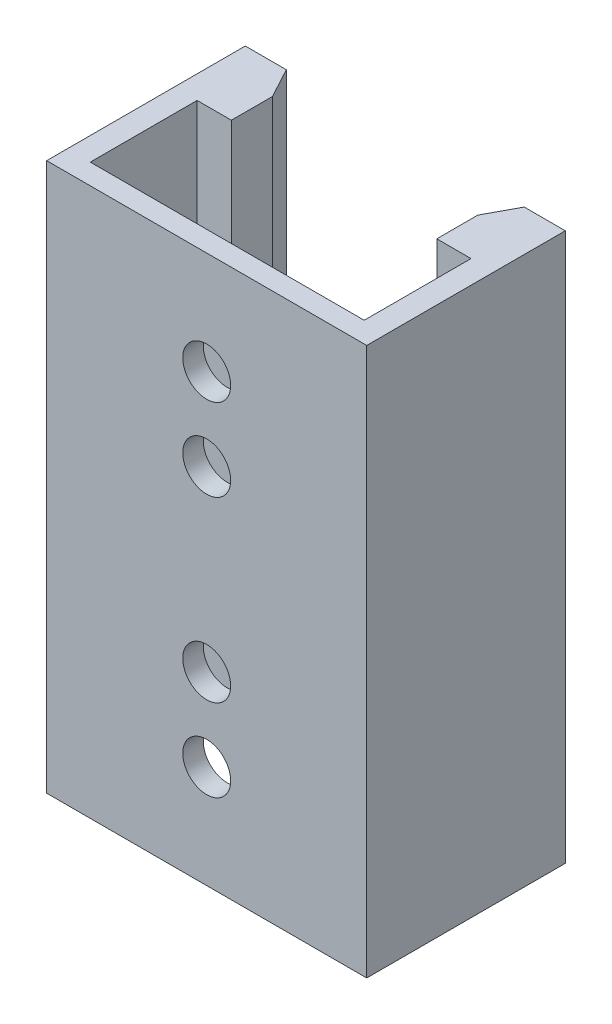
SolidWorks part; units mm, degrees
ref_plane "Front Plane" through (0, 0, 0) normal (0, 0, 1) x (1, 0, 0)
ref_plane "Top Plane" through (0, 0, 0) normal (0, 1, 0) x (1, 0, 0)
ref_plane "Right Plane" through (0, 0, 0) normal (1, 0, 0) x (0, 0, -1)
sketch "Sketch1" plane through (0, 0, 0) normal (0, 1, 0) x (1, 0, 0)
  line L0 (-11.6838, 0) -> (11.6838, 0)
  line L1 (11.6838, 0) -> (11.6838, 14.5)
  line L2 (11.6838, 14.5) -> (8.6838, 14.5)
  line L3 (8.6838, 14.5) -> (7.5, 12.3)
  line L4 (7.5, 12.3) -> (7.5, 9.3)
  line L5 (7.5, 9.3) -> (10, 9.3)
  line L6 (10, 9.3) -> (10, 1.5)
  line L7 (10, 1.5) -> (-10, 1.5)
  line L8 (0, 1.5) -> (0, 0)
  line L9 (-10, 9.3) -> (-10, 1.5)
  line L10 (-7.5, 9.3) -> (-10, 9.3)
  line L11 (-7.5, 12.3) -> (-7.5, 9.3)
  line L12 (-8.6838, 14.5) -> (-7.5, 12.3)
  line L13 (-11.6838, 14.5) -> (-8.6838, 14.5)
  line L14 (-11.6838, 0) -> (-11.6838, 14.5)
  dimension "D1" = 10
  dimension "D2" = 7.8
  dimension "D3" = 2.5
  dimension "D4" = 3
  dimension "D5" = 2.2
  dimension "D6" = 3
  dimension "D7" = 14.5
extrude "Boss-Extrude1" add sketch "Sketch1" along normal blind 40 contours L7 L9 L10 L11 L12 L13 L14 L0 L1 L2 L3 L4 L5 L6
sketch "Sketch2" plane through (0, 0, 0) normal (0, 0, 1) x (1, 0, 0)
  line L0 (-11.6838, 20) -> (11.6838, 20) construction
  line L1 (-11.6838, 40) -> (-11.6838, 0) construction
  line L2 (11.6838, 40) -> (11.6838, 0) construction
  line L3 (0, 40) -> (0, 0) construction
  line L4 (-11.6838, 40) -> (11.6838, 40) construction
  circle A0 centre (0, 7.5) radius 1.75
  circle A1 centre (0, 26.5) radius 1.75
  circle A2 centre (0, 13.5) radius 1.75
  circle A3 centre (0, 32.5) radius 1.75
  dimension "D1" = 19
  dimension "D2" = 19
  dimension "D3" = 3.5
  dimension "D4" = 6.5
  dimension "D5" = 6.5
extrude "Cut-Extrude1" cut sketch "Sketch2" against normal blind 10 contours A1 | A0 | A3 | A2
